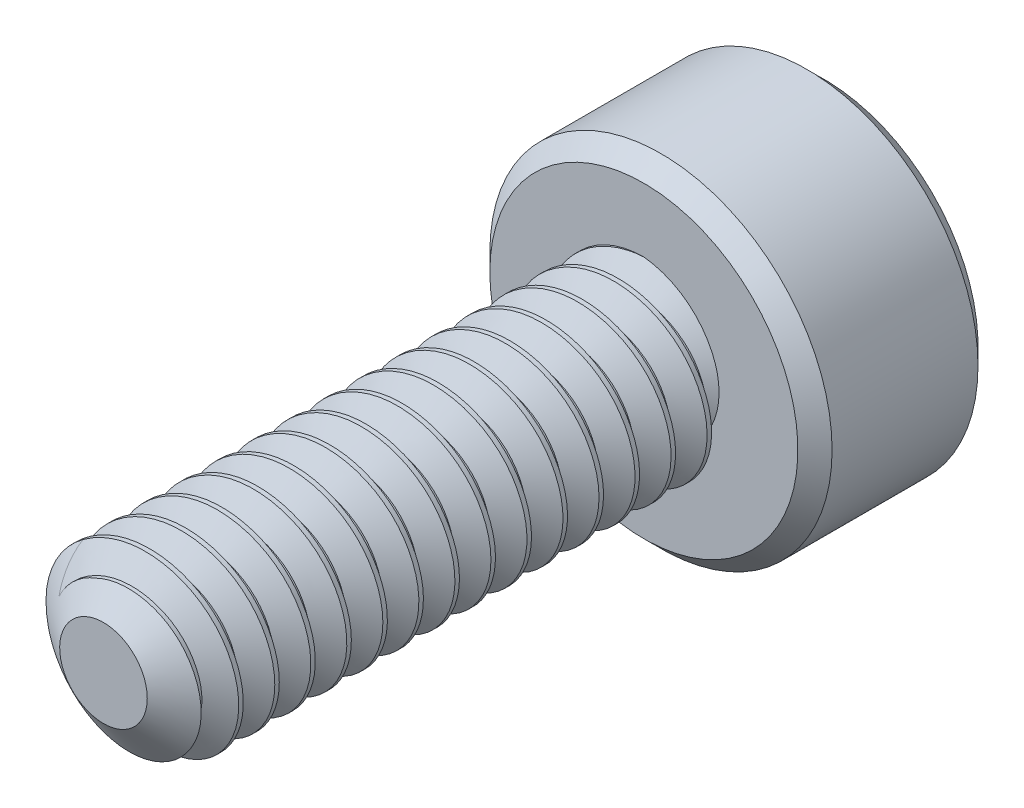
SolidWorks part; units mm, degrees
ref_plane "Front Plane" through (0, 0, 0) normal (0, 0, 1) x (1, 0, 0)
ref_plane "Top Plane" through (0, 0, 0) normal (0, 1, 0) x (1, 0, 0)
ref_plane "Right Plane" through (0, 0, 0) normal (1, 0, 0) x (0, 0, -1)
sketch "Sketch1" plane through (0, 0, 0) normal (0, 0, 1) x (1, 0, 0)
  circle A0 centre (0, 0) radius 1
  dimension "OD" = 2
extrude "Shaft Extrude" add sketch "Sketch1" against normal blind 6
sketch "Sketch2" plane through (0, 0, 0) normal (0, 0, 1) x (1, 0, 0)
  circle A0 centre (0, 0) radius 1 construction
  circle A1 centre (0, 0) radius 1
curve "Thread Helix/Spiral" pitch 0.4 height 6.4 radius 1 centre (0, 0, 0) axis (0, 0, -1) start towards (0, 1, 0) parameters "pitch"=0.4
sketch "Sketch3" plane through (0, 0, 0) normal (1, 0, 0) x (0, 0, -1)
  line L0 (-0.35, 1) -> (-0.2, 0.7402)
  line L1 (-0.2, 0.7402) -> (-0.15, 0.7402)
  line L2 (-0.15, 0.7402) -> (0, 1)
  line L3 (-0.35, 1) -> (0, 1)
  line L4 (-0.175, 1) -> (-0.175, 0.7402) construction
  line L5 (-0.275, 0.8701) -> (-0.075, 0.8701) construction
  line L6 (0, 1) -> (0, -1) construction
  dimension "D1" = 0.05
  dimension "D2" = 0.2
  dimension "D3" = 60
sweep "Thread Cut Sweep" cut profiles "Sketch3" path "Thread Helix/Spiral" align with end faces yes
sketch "Sketch4" plane through (0, 0, 0) normal (1, 0, 0) x (0, 0, -1)
  line L0 (0.3598, 1) -> (0, 0.4862)
  line L1 (0, 0.4862) -> (0, 1)
  line L2 (0.3598, 1) -> (0, 1)
  line L3 (-0.35, 1) -> (0, 1) construction
  line L4 (0, 0) -> (7.0209, 0) construction
  dimension "D1" = 55
  dimension "D2" = 0.254
revolve "End Cut Revolve" cut sketch "Sketch4" angle 360 about L4
sketch "Sketch6" plane through (0, 0, -6) normal (0, 0, -1) x (-1, 0, 0)
  circle A0 centre (0, 0) radius 1.9
  dimension "head dia" = 3.8
extrude "Head Extrude" add sketch "Sketch6" along normal blind 2
sketch "Sketch7" plane through (0, 0, -8) normal (0, 0, -1) x (-1, 0, 0)
  line L1 (0, 0.866) -> (-0.75, 0.433)
  line L2 (-0.75, 0.433) -> (-0.75, -0.433)
  line L3 (-0.75, -0.433) -> (0, -0.866)
  line L4 (0, -0.866) -> (0.75, -0.433)
  line L5 (0.75, -0.433) -> (0.75, 0.433)
  line L6 (0.75, 0.433) -> (0, 0.866)
  circle A0 centre (0, 0) radius 0.75 construction
  dimension "hex dia" = 1.5
extrude "Socket Cut Extrude" cut sketch "Sketch7" against normal blind 1.125
sketch "Sketch8" plane through (0, 0, -8) normal (0, 0, -1) x (-1, 0, 0)
  circle A0 centre (0, 0) radius 0.866
extrude "Socket Entry Cut Extrude" cut sketch "Sketch8" against normal through all draft 45
chamfer "Head Chamfer" distance 0.19 angle 45 2 edges at (-1.9, 0, -8) (-1.9, 0, -6)
sketch "Sketch10" plane through (0, 0, -6) normal (0, 0, 1) x (1, 0, 0)
  circle A1 centre (0, 0) radius 1
  circle A2 centre (0, 0) radius 1
  dimension "D1" = 0
ref_plane "Partial Thread Plane" through (0, 0, -17) normal (0, 0, 1) x (1, 0, 0)
extrude "Partial Thread Extrude" [suppressed] add sketch "Sketch10" along normal up to surface (1 mm away) separate body up to plane "Partial Thread Plane"
chamfer "Partial Thread Chamfer" [suppressed] distance 0.04 angle 45
combine bodies "Partial Thread Combine" [suppressed] operation type add bodies to combine 107 108
equation "\"D3@Thread Helix/Spiral\" = \"screw length@Shaft Extrude\" + \"pitch@Thread Helix/Spiral\""
equation "\"D1@Sketch3\" = \"pitch@Thread Helix/Spiral\" * .125"
equation "\"D2@Sketch3\" = \"pitch@Thread Helix/Spiral\" * .5"
equation "\"D1@Socket Cut Extrude\" = \"hex dia@Sketch7\" * .75"
equation "\"D1@Head Chamfer\" = \"head dia@Sketch6\" * .05"
equation "\"D1@Partial Thread Chamfer\" = \"OD@Sketch1\" * .02"
